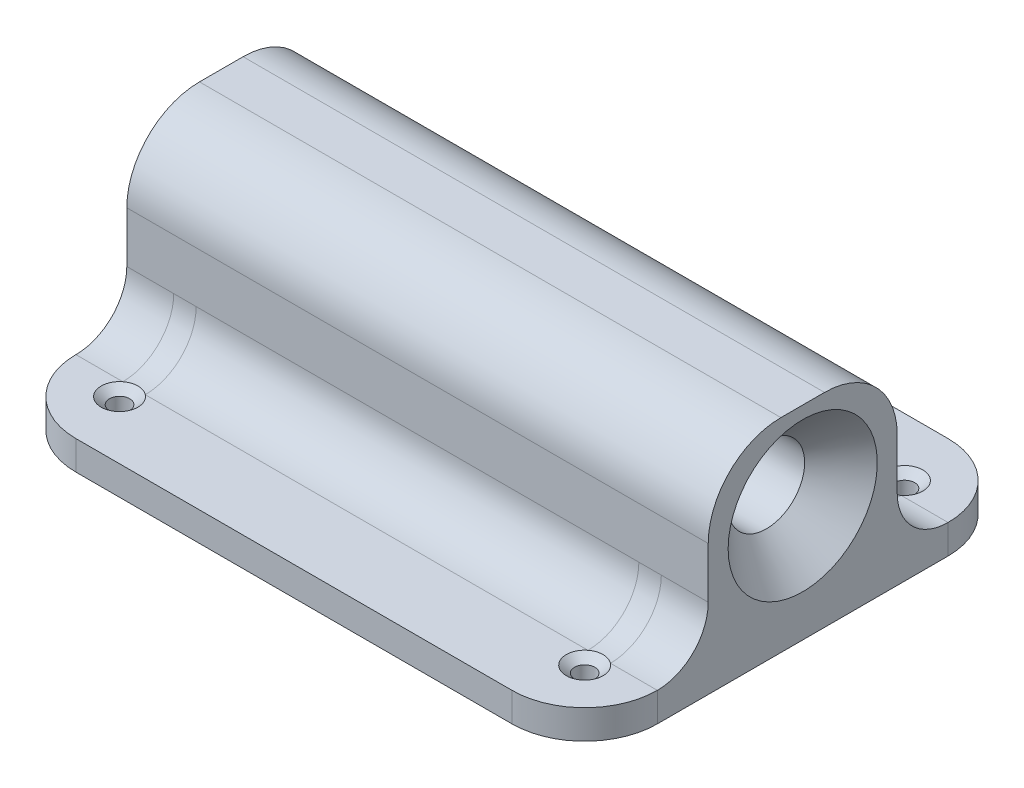
SolidWorks part; units mm, degrees
ref_plane "Front Plane" through (0, 0, 0) normal (0, 0, 1) x (1, 0, 0)
ref_plane "Top Plane" through (0, 0, 0) normal (0, 1, 0) x (1, 0, 0)
ref_plane "Right Plane" through (0, 0, 0) normal (1, 0, 0) x (0, 0, -1)
sketch "Sketch1" plane through (0, 0, 0) normal (0, 1, 0) x (1, 0, 0)
  line L1 (-40, -30) -> (40, -30)
  line L2 (-40, -30) -> (-40, 30)
  line L3 (-40, 30) -> (40, 30)
  line L4 (40, -30) -> (40, 30)
  line L5 (-40, -30) -> (40, 30) construction
  line L6 (-40, 30) -> (40, -30) construction
  point P0 (0, 0)
  dimension "D1" = 80
  dimension "D2" = 60
extrude "Base" add sketch "Sketch1" along normal blind 4
sketch "Sketch3" plane through (0, 4, 0) normal (0, 1, 0) x (1, 0, 0)
  line L0 (40, -30) -> (40, 30) construction
  line L1 (-40, -13) -> (40, -13)
  line L2 (-40, -13) -> (-40, 13)
  line L3 (-40, 13) -> (40, 13)
  line L4 (40, -13) -> (40, 13)
  line L5 (-40, -13) -> (40, 13) construction
  line L6 (-40, 13) -> (40, -13) construction
  point P0 (0, 0)
  dimension "D1" = 26
extrude "Pin block" add sketch "Sketch3" along normal blind 24
sketch "Sketch7" plane through (40, 0, 0) normal (1, 0, 0) x (0, 0, -1)
  line L0 (13, 16) -> (-13, 16) construction
  line L1 (13, 28) -> (13, 4) construction
  line L2 (-13, 28) -> (-13, 4) construction
  circle A0 centre (0, 16) radius 5.2625
  dimension "D1" = 10.525
extrude "Pin hole" cut sketch "Sketch7" against normal through all
sketch "Screw hole placement" plane through (0, 4, 0) normal (0, 1, 0) x (1, 0, 0)
  line L0 (40, -30) -> (40, -13) construction
  line L3 (-40, -30) -> (40, -30) construction
  point P0 (32, -22)
  dimension "D1" = 8
  dimension "D2" = 8
hole_wizard "CSK for #3 Flat Head Machine Screw (100)1" positions "Sketch5" profile "Sketch6" countersink size "#3" standard "ANSI Inch" end condition through all
sketch "Sketch5" plane through (0, 4, 0) normal (0, 1, 0) x (1, 0, 0)
  point P0 (32, -22)
sketch "Sketch6" plane through (32, 4, 22) normal (1, 0, 0) x (0, 0, 1)
  line L0 (0, 0) -> (0, 4)
  line L1 (0, 4) -> (1.397, 4)
  line L2 (1.397, 4) -> (1.397, 0.9484)
  line L3 (1.397, 0.9484) -> (2.5273, 0)
  line L5 (2.5273, 0) -> (0, 0)
  line L6 (-1.397, 0.9484) -> (-2.5273, 0) construction
  line L11 (0, -6.35) -> (0, 107.95) construction
  dimension "Thru Hole Dia." = 2.794
  dimension "Thru Hole Depth" = 4
  dimension "Near C'Sink Dia." = 5.0546
  dimension "Near C'Sink Angle" = 100
mirror "Mirror1" about plane through (0, 0, 0) normal (1, 0, 0) of "CSK for #3 Flat Head Machine Screw (100)1"
mirror "Mirror2" about plane through (0, 0, 0) normal (0, 0, 1) of "CSK for #3 Flat Head Machine Screw (100)1", "Mirror1"
fillet "Fillet2" radius 10 4 edges at (-40, 2, -30) (40, 2, -30) (40, 2, 30) (-40, 2, 30)
fillet "Fillet3" radius 10 2 edges at (0, 28, -13) (0, 28, 13)
chamfer "Chamfer1" distance 5 angle 45 1 edges at (40, 16, -5.2625)
fillet "Fillet4" radius 7 2 edges at (0, 4, -13) (0, 4, 13)
